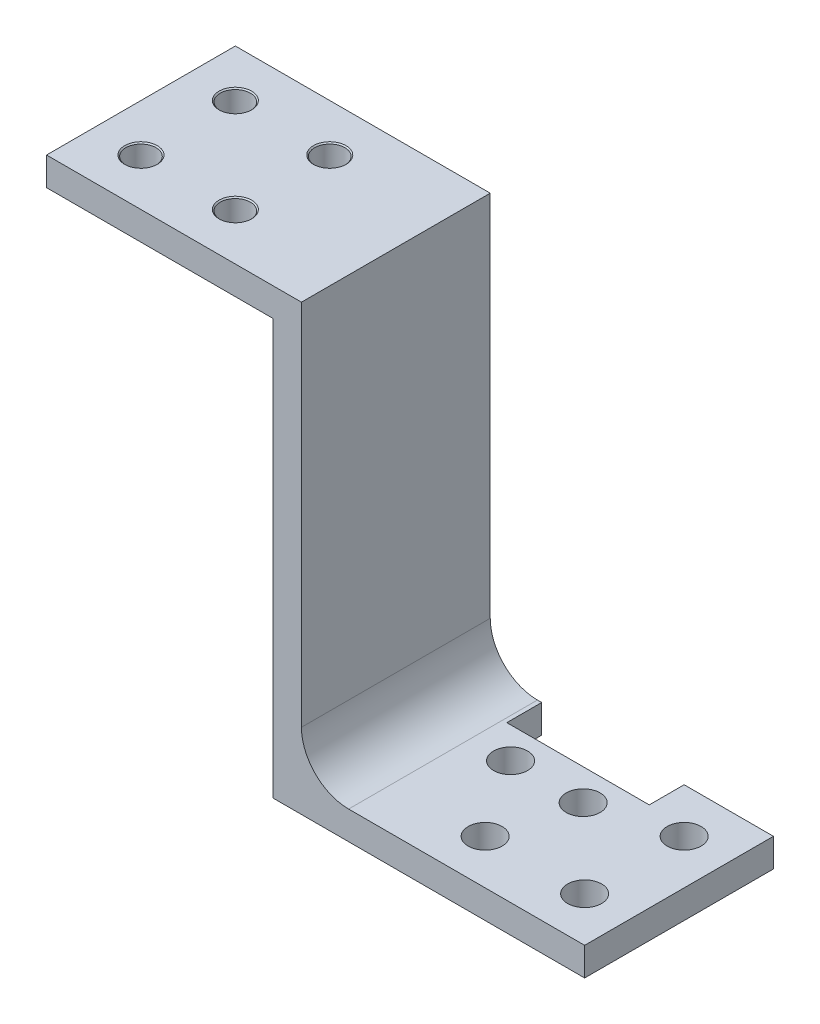
SolidWorks part; units mm, degrees
ref_plane "Front Plane" through (0, 0, 0) normal (0, 0, 1) x (1, 0, 0)
ref_plane "Top Plane" through (0, 0, 0) normal (0, 1, 0) x (1, 0, 0)
ref_plane "Right Plane" through (0, 0, 0) normal (1, 0, 0) x (0, 0, -1)
sketch "Sketch1" plane through (0, 0, 0) normal (0, 0, 1) x (1, 0, 0)
  line L0 (0, 44) -> (24, 44)
  line L1 (24, 44) -> (24, 0)
  line L2 (24, 0) -> (57, 0)
  line L3 (57, 0) -> (57, 3)
  line L4 (57, 3) -> (27, 3)
  line L5 (27, 3) -> (27, 47)
  line L6 (27, 47) -> (0, 47)
  line L7 (0, 47) -> (0, 44)
  line L8 (24, 25) -> (27, 25) construction
  point P12 (27, 25)
  dimension "D1" = 3
  dimension "D2" = 24
  dimension "D3" = 44
  dimension "D4" = 30
extrude "Boss-Extrude1" add sketch "Sketch1" along normal blind 20
hole_wizard "M3 Clearance Hole1" positions "Sketch2" profile "Sketch3" hole size "M3" standard "ANSI Metric" end condition through all
sketch "Sketch2" plane through (0, 47, 0) normal (0, 1, 0) x (1, 0, 0)
  line L0 (0, -10) -> (20, -10) construction
  line L1 (0, -20) -> (0, 0) construction
  line L4 (10, 0) -> (10, -20) construction
  line L7 (24, -20) -> (24, 0) construction
  line L8 (24, -20) -> (24, 0) construction
  line L9 (27, -20) -> (0, -20) construction
  point P17 (5, -5)
  point P25 (5, -15)
  point P26 (15, -5)
  point P27 (15, -15)
  point P37 (10, -10)
  dimension "D1" = 5
  dimension "D2" = 5
  dimension "D3" = 20
sketch "Sketch3" plane through (15, 47, 15) normal (1, 0, 0) x (0, 0, 1)
  line L0 (0, 0) -> (0, 47)
  line L1 (0, 47) -> (1.6, 47)
  line L2 (1.6, 47) -> (1.6, 0.125)
  line L3 (1.6, 0.125) -> (1.725, 0)
  line L5 (1.725, 0) -> (0, 0)
  line L6 (-1.6, 0.125) -> (-1.725, 0) construction
  line L11 (0, -6.35) -> (0, 107.95) construction
  dimension "Thru Hole Dia." = 3.2
  dimension "Thru Hole Depth" = 47
  dimension "Near C'Sink Dia." = 3.45
  dimension "Near C'Sink Angle" = 90
sketch "Sketch4" plane through (0, 3, 0) normal (0, 1, 0) x (1, 0, 0)
  line L0 (57, 0) -> (27, 0) construction
  line L1 (32.4508, 0) -> (47.5398, 0)
  line L2 (32.4508, 0) -> (32.4508, -3.6956)
  line L3 (32.4508, -3.6956) -> (47.5398, -3.6956)
  line L4 (47.5398, 0) -> (47.5398, -3.6956)
  line L5 (32.6508, -10.4956) -> (32.6508, -3.4956) construction
  line L6 (47.3398, -10.4956) -> (47.3398, -3.4956) construction
  line L7 (32.6508, -10.4956) -> (32.6508, -3.4956) construction
  line L8 (47.3398, -10.4956) -> (47.3398, -3.4956) construction
  line L9 (32.6508, -3.4956) -> (47.3398, -3.4956) construction
  point P10 (39.9953, -3.6956)
  point P11 (39.9953, -3.4956)
  dimension "D1" = 0.2
  dimension "D2" = 0.2
extrude "Cut-Extrude1" cut sketch "Sketch4" against normal through all
sketch "Sketch5" plane through (0, 3, 0) normal (0, 1, 0) x (1, 0, 0)
  point P0 (36.1508, -6.9956)
  point P3 (43.8398, -6.9956)
hole_wizard "M3 Clearance Hole2" positions "Sketch5" profile "Sketch6" hole size "M3" standard "ANSI Metric" end condition through all
sketch "Sketch6" plane through (36.1508, 3, 6.9956) normal (1, 0, 0) x (0, 0, 1)
  line L0 (0, 0) -> (0, 3)
  line L1 (0, 3) -> (1.8, 3)
  line L2 (1.8, 3) -> (1.8, 0)
  line L5 (1.8, 0) -> (0, 0)
  line L11 (0, -6.35) -> (0, 107.95) construction
  dimension "Thru Hole Dia." = 3.6
  dimension "Thru Hole Depth" = 3
sketch "Sketch9" plane through (0, 3, 0) normal (0, 1, 0) x (1, 0, 0)
  line L0 (57, -20) -> (27, -20) construction
  line L1 (57, -20) -> (57, 0) construction
  line L2 (57, 0) -> (47.5398, 0) construction
  line L3 (47.5398, -3.6956) -> (47.5398, 0) construction
  line L4 (57, -20) -> (27, -20)
  line L5 (57, -20) -> (57, 0)
  line L6 (57, 0) -> (47.5398, 0)
  line L7 (47.5398, -3.6956) -> (47.5398, 0)
  line L8 (47.5398, -3.6956) -> (47.5398, -10.5398)
  line L9 (47.5398, -10.5398) -> (37, -10.5398)
  line L10 (37, -10.5398) -> (37, -20)
  line L11 (52.2699, 0) -> (52.2699, -4.7301) construction
  line L12 (52.2699, -4.7301) -> (52.2699, -15.2699) construction
  line L13 (52.2699, -15.2699) -> (52.2699, -20) construction
  line L14 (37, -15.2699) -> (41.7301, -15.2699) construction
  line L15 (41.7301, -15.2699) -> (52.2699, -15.2699) construction
  line L16 (52.2699, -15.2699) -> (57, -15.2699) construction
  circle A0 centre (52.2699, -4.7301) radius 1.75
  circle A1 centre (52.2699, -15.2699) radius 1.75
  circle A2 centre (41.7301, -15.2699) radius 1.75
  point P11 (52.2699, 0)
  point P18 (37, -15.2699)
  dimension "D1" = 3.5
  dimension "D2" = 3.5
  dimension "D3" = 3.5
sketch "Sketch10" plane through (0, 3, 0) normal (0, 1, 0) x (1, 0, 0)
  point P0 (41.7301, -15.2699)
  point P3 (52.2699, -15.2699)
  point P6 (52.2699, -4.7301)
hole_wizard "M3 Clearance Hole3" positions "Sketch10" profile "Sketch11" hole size "M3" standard "ANSI Metric" end condition through all
sketch "Sketch11" plane through (41.7301, 3, 15.2699) normal (1, 0, 0) x (0, 0, 1)
  line L0 (0, 0) -> (0, 3)
  line L1 (0, 3) -> (1.8, 3)
  line L2 (1.8, 3) -> (1.8, 0)
  line L5 (1.8, 0) -> (0, 0)
  line L11 (0, -6.35) -> (0, 107.95) construction
  dimension "Thru Hole Dia." = 3.6
  dimension "Thru Hole Depth" = 3
fillet "Fillet1" radius 5 1 edges at (27, 3, 10)
